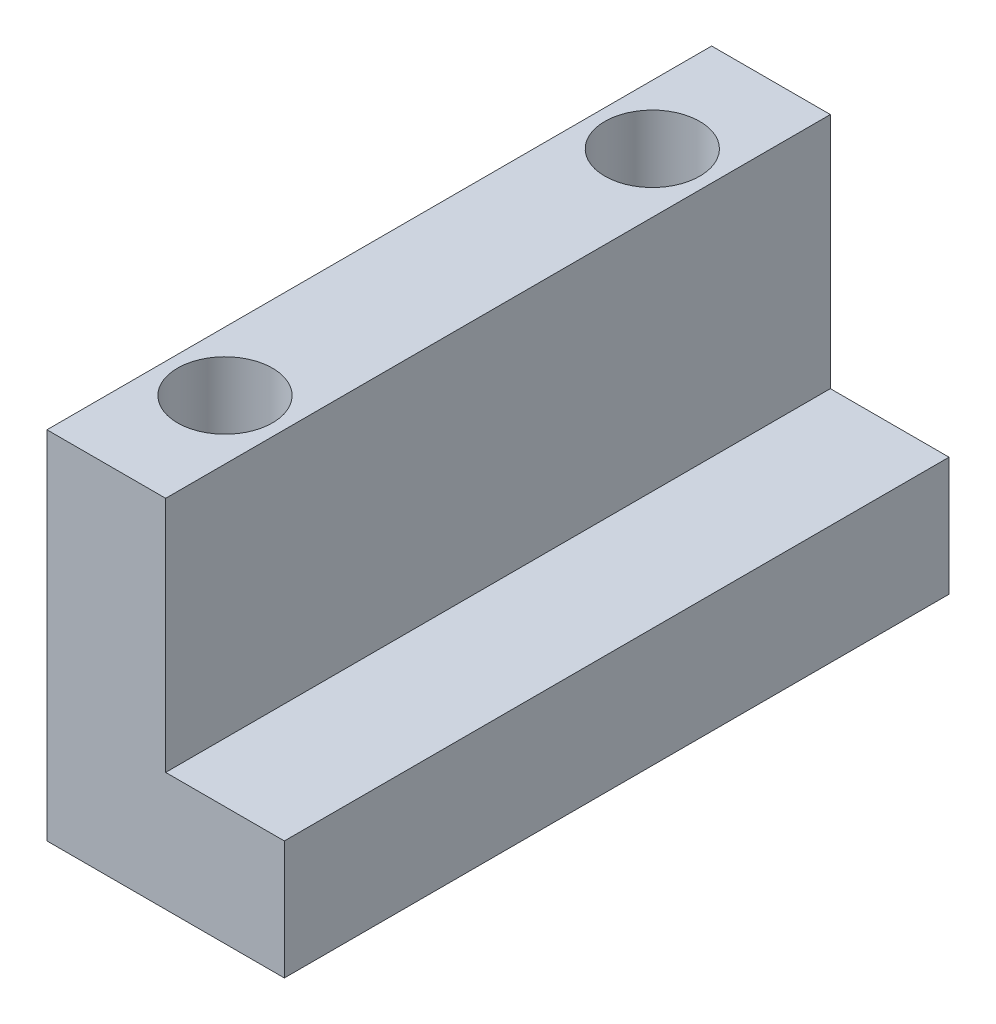
SolidWorks part; units mm, degrees
other "Markup1"
sketch "Sketch6" plane through (0, 0, 0) normal (0.7258, -0.6292, 0.2781) x (-0.261, -0.6259, -0.735)
ref_plane "Front Plane" through (0, 0, 0) normal (0, 0, 1) x (1, 0, 0)
ref_plane "Top Plane" through (0, 0, 0) normal (0, 1, 0) x (1, 0, 0)
ref_plane "Right Plane" through (0, 0, 0) normal (1, 0, 0) x (0, 0, -1)
sketch "Sketch1" plane through (0, 0, 0) normal (0, 0, 1) x (1, 0, 0)
  line L0 (0, 0) -> (-12.7, 0)
  line L1 (-12.7, 0) -> (-12.7, 19.05)
  line L2 (-12.7, 19.05) -> (-6.35, 19.05)
  line L3 (-6.35, 19.05) -> (-6.35, 6.35)
  line L4 (-6.35, 6.35) -> (0, 6.35)
  line L5 (0, 6.35) -> (0, 0)
  dimension "D1" = 6.35
  dimension "D2" = 6.35
  dimension "D3" = 6.35
  dimension "D4" = 12.7
extrude "Boss-Extrude1" add sketch "Sketch1" against normal blind 381
sketch "Sketch2" plane through (-12.7, 0, 0) normal (-1, 0, 0) x (0, 0, 1)
  line L0 (-381, 0) -> (0, 0) construction
  line L2 (0, 19.05) -> (0, 0) construction
  circle A0 centre (-365.76, 12.065) radius 3.175
  dimension "D1" = 6.35
  dimension "D2" = 12.065
  dimension "D3" = 365.76
extrude "Cut-Extrude1" cut sketch "Sketch2" against normal up to next
sketch "Sketch3" plane through (0, 19.05, 0) normal (0, 1, 0) x (1, 0, 0)
  line L0 (-9.525, 381) -> (-9.525, 0) construction
  line L1 (-6.35, 381) -> (-12.7, 381) construction
  line L2 (-6.35, 0) -> (-12.7, 0) construction
  circle A0 centre (-9.525, 6.35) radius 2.54
  circle A1 centre (-9.525, 374.65) radius 2.54
  dimension "D1" = 5.08
  dimension "D3" = 6.35
  dimension "D2" = 6.35
extrude "Cut-Extrude2" cut sketch "Sketch3" against normal blind 7.62
sketch "Sketch4" plane through (0, 0, 0) normal (0, -1, 0) x (1, 0, 0)
  line L0 (-9.525, 0) -> (-9.525, -381) construction
  line L1 (-12.7, 0) -> (0, 0) construction
  line L2 (-12.7, -381) -> (0, -381) construction
  line L3 (0, -381) -> (0, 0) construction
  circle A0 centre (-9.525, -374.65) radius 2.54
  circle A1 centre (-9.525, -6.35) radius 2.54
  dimension "D2" = 5.08
  dimension "D1" = 9.525
  dimension "D3" = 6.35
  dimension "D4" = 6.35
extrude "Cut-Extrude3" cut sketch "Sketch4" against normal blind 7.62
sketch "Sketch5" plane through (0, 0, -381) normal (0, 0, -1) x (-1, 0, 0)
  line L1 (6.35, 6.35) -> (0, 6.35)
  line L2 (6.35, 6.35) -> (6.35, 0)
  line L3 (6.35, 0) -> (0, 0)
  line L4 (0, 6.35) -> (0, 0)
extrude "Cut-Extrude4" cut sketch "Sketch5" against normal blind 345.44
sketch "Sketch7" plane through (-6.35, 0, 0) normal (1, 0, 0) x (0, 0, -1)
  line L0 (35.56, 0) -> (381, 0) construction
  line L1 (35.56, 0) -> (381, 0)
  line L2 (35.56, 0) -> (35.56, 19.05)
  line L3 (35.56, 19.05) -> (381, 19.05)
  line L4 (381, 0) -> (381, 19.05)
extrude "Cut-Extrude5" cut sketch "Sketch7" against normal through all
sketch "Sketch8" plane through (0, 19.05, 0) normal (0, 1, 0) x (1, 0, 0)
  line L0 (-12.7, 35.56) -> (-6.35, 35.56) construction
  line L1 (-12.7, 35.56) -> (-12.7, 0) construction
  circle A0 centre (-9.525, 29.21) radius 2.54
  point P4 (0, 0)
  dimension "D1" = 5.08
  dimension "D2" = 6.35
  dimension "D3" = 3.175
extrude "Cut-Extrude6" cut sketch "Sketch8" against normal through all
